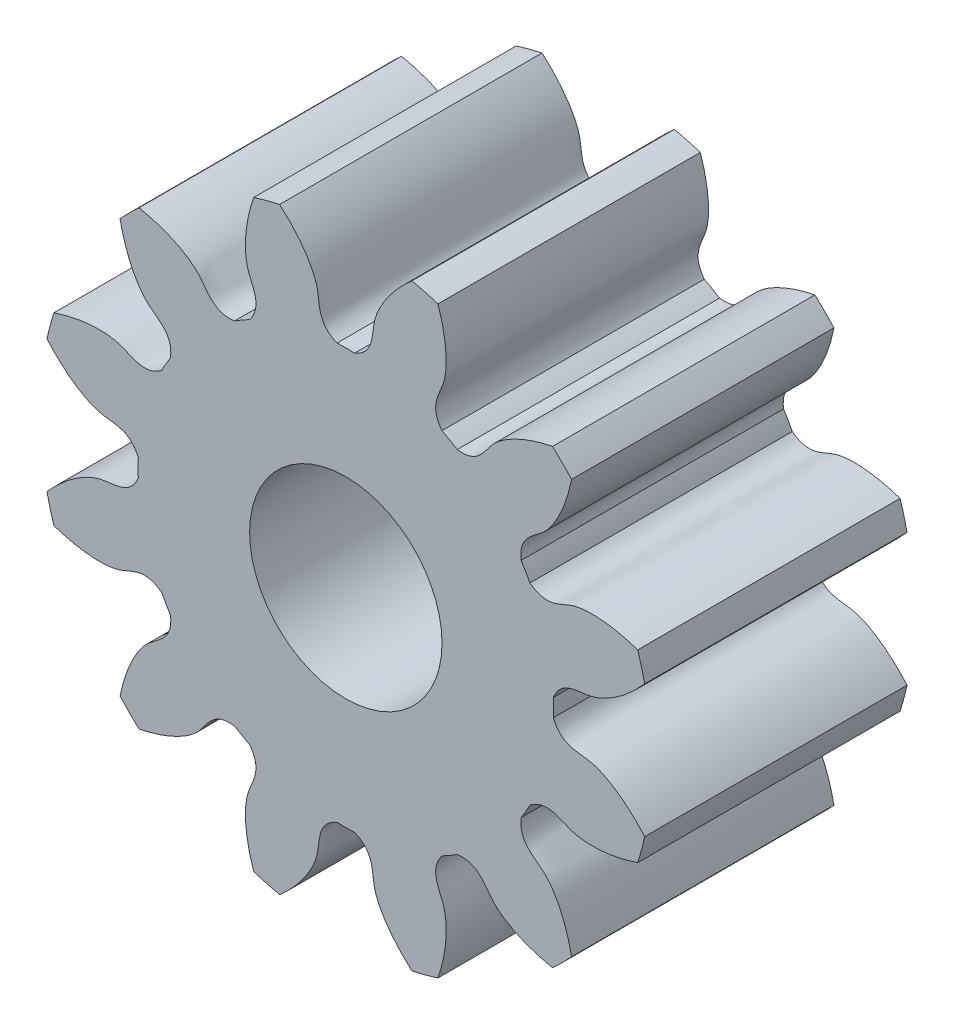
SolidWorks part; units mm, degrees
ref_plane "前视基准面" through (0, 0, 0) normal (0, 0, 1) x (1, 0, 0)
ref_plane "上视基准面" through (0, 0, 0) normal (0, 1, 0) x (1, 0, 0)
ref_plane "右视基准面" through (0, 0, 0) normal (1, 0, 0) x (0, 0, -1)
other "Configuration Table"
sketch "草图1" plane through (0, 0, 0) normal (0, 0, 1) x (1, 0, 0)
  circle A0 centre (0, 0) radius 3.5
extrude "凸台-拉伸1" add sketch "草图1" along normal blind 3
ref_axis "基准轴1" through (0, 0, 3) along (0, 0, -1)
sketch "草图2" plane through (0, 0, 0) normal (0, 0, 1) x (1, 0, 0)
  line L0 (0, 0) -> (0, 3.5) construction
  circle A0 centre (0, 0) radius 3.5 construction
  arc A1 (0.1004, 2.3729) -> (-0.1004, 2.3729) centre (0, 0) ccw
  arc A2 (1.7488, 3.9475) -> (-1.7488, 3.9475) centre (0, 0) ccw
  spline S0 degree 3 poles (0.1004, 2.3729) (0.3404, 2.4747) (0.2872, 2.6724) (0.3381, 2.8447) (0.3413, 2.855) (0.3451, 2.8662) (0.3495, 2.8784) (0.3546, 2.8915) (0.3603, 2.9056) (0.3668, 2.9206) (0.374, 2.9366) (0.3821, 2.9533) (0.3909, 2.971) (0.4007, 2.9894) (0.4114, 3.0086) (0.423, 3.0286) (0.4356, 3.0493) (0.4492, 3.0707) (0.4639, 3.0928) (0.4796, 3.1155) (0.4965, 3.1388) (0.5145, 3.1626) (0.5337, 3.187) (0.554, 3.2119) (0.5756, 3.2372) (0.5985, 3.2629) (0.6226, 3.289) (0.648, 3.3154) (0.6748, 3.342) (0.7028, 3.369) (0.7323, 3.3961) (0.7631, 3.4234) (0.7954, 3.4507) (0.829, 3.4782) (0.8641, 3.5057) (0.9006, 3.5331) (0.9385, 3.5604) (0.978, 3.5877) (1.0189, 3.6147) (1.0613, 3.6416) (1.1052, 3.6681) (1.1506, 3.6944) (1.1975, 3.7203) (1.2459, 3.7457) (1.2958, 3.7707) (1.3472, 3.7952) (1.4001, 3.8191) (1.4546, 3.8424) (1.5105, 3.865) (1.5679, 3.8869) (1.6472, 3.9154) (1.7078, 3.9351) (1.7488, 3.9475) knots 0 0 0 0 0.218015 0.222044 0.226546 0.231522 0.236972 0.242897 0.249295 0.256167 0.263513 0.271332 0.279626 0.288394 0.297636 0.307351 0.317541 0.328204 0.339341 0.350953 0.363038 0.375597 0.38863 0.402137 0.416118 0.430573 0.445502 0.460904 0.476781 0.493132 0.509956 0.527255 0.545027 0.563273 0.581994 0.601188 0.620856 0.640998 0.661614 0.682704 0.704268 0.726305 0.748817 0.771803 0.795262 0.819196 0.843603 0.868484 0.89384 0.919669 0.945972 1 1 1 1
  spline S1 degree 3 poles (-0.1004, 2.3729) (-0.3404, 2.4747) (-0.2872, 2.6724) (-0.3381, 2.8447) (-0.3413, 2.855) (-0.3451, 2.8662) (-0.3495, 2.8784) (-0.3546, 2.8915) (-0.3603, 2.9056) (-0.3668, 2.9206) (-0.374, 2.9366) (-0.3821, 2.9533) (-0.3909, 2.971) (-0.4007, 2.9894) (-0.4114, 3.0086) (-0.423, 3.0286) (-0.4356, 3.0493) (-0.4492, 3.0707) (-0.4639, 3.0928) (-0.4796, 3.1155) (-0.4965, 3.1388) (-0.5145, 3.1626) (-0.5337, 3.187) (-0.554, 3.2119) (-0.5756, 3.2372) (-0.5985, 3.2629) (-0.6226, 3.289) (-0.648, 3.3154) (-0.6748, 3.342) (-0.7028, 3.369) (-0.7323, 3.3961) (-0.7631, 3.4234) (-0.7954, 3.4507) (-0.829, 3.4782) (-0.8641, 3.5057) (-0.9006, 3.5331) (-0.9385, 3.5604) (-0.978, 3.5877) (-1.0189, 3.6147) (-1.0613, 3.6416) (-1.1052, 3.6681) (-1.1506, 3.6944) (-1.1975, 3.7203) (-1.2459, 3.7457) (-1.2958, 3.7707) (-1.3472, 3.7952) (-1.4001, 3.8191) (-1.4546, 3.8424) (-1.5105, 3.865) (-1.5679, 3.8869) (-1.6472, 3.9154) (-1.7078, 3.9351) (-1.7488, 3.9475) knots 0 0 0 0 0.218015 0.222044 0.226546 0.231522 0.236972 0.242897 0.249295 0.256167 0.263513 0.271332 0.279626 0.288394 0.297636 0.307351 0.317541 0.328204 0.339341 0.350953 0.363038 0.375597 0.38863 0.402137 0.416118 0.430573 0.445502 0.460904 0.476781 0.493132 0.509956 0.527255 0.545027 0.563273 0.581994 0.601188 0.620856 0.640998 0.661614 0.682704 0.704268 0.726305 0.748817 0.771803 0.795262 0.819196 0.843603 0.868484 0.89384 0.919669 0.945972 1 1 1 1
extrude "切除-拉伸1" cut sketch "草图2" along normal through all
pattern_circular "阵列(圆周)1" count 12 every 30 about axis through (0, 0, 3) along (0, 0, -1) of "切除-拉伸1"
sketch "草图3" plane through (0, 0, 0) normal (0, 0, 1) x (1, 0, 0)
  circle A0 centre (0, 0) radius 3 construction
  dimension "Dn" = 6
sketch "草图4" plane through (0, 0, 3) normal (0, 0, 1) x (1, 0, 0)
  circle A0 centre (0, 0) radius 1.1
  dimension "D1" = 2.2
extrude "切除-拉伸2" cut sketch "草图4" against normal up to next
